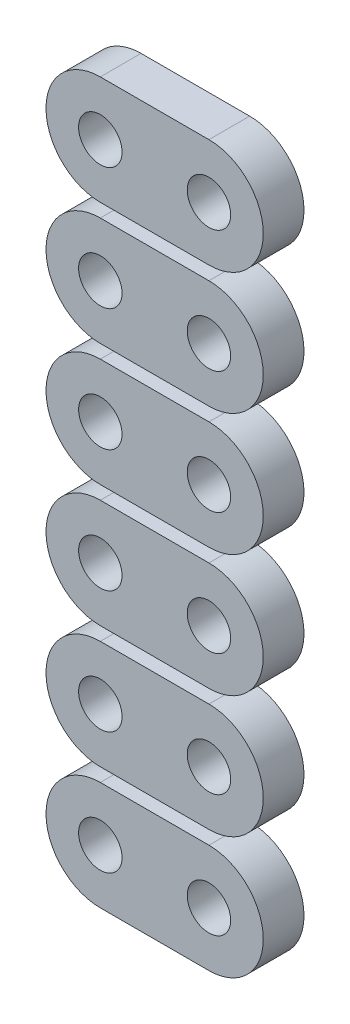
SolidWorks part; units mm, degrees
ref_plane "Front Plane" through (0, 0, 0) normal (0, 0, 1) x (1, 0, 0)
ref_plane "Top Plane" through (0, 0, 0) normal (0, 1, 0) x (1, 0, 0)
ref_plane "Right Plane" through (0, 0, 0) normal (1, 0, 0) x (0, 0, -1)
ref_axis "Axis2" through (-8.8, 0, 0) along (1, 0, 0)
ref_axis "Axis3" through (0, 4.4, 0) along (0, -1, 0)
sketch "Sketch1" plane through (0, 0, 0) normal (0, 0, 1) x (1, 0, 0)
  line L0 (-4, 0) -> (4, 0) construction
  line L1 (-4, 4) -> (4, 4)
  line L2 (-4, -4) -> (4, -4)
  arc A0 (-4, 4) -> (-4, -4) centre (-4, 0) ccw
  arc A1 (4, -4) -> (4, 4) centre (4, 0) ccw
  circle A2 centre (-4, 0) radius 1.6
  circle A3 centre (4, 0) radius 1.6
  point P2 (0, 0)
  dimension "D2" = 3.2
  dimension "D3" = 4
  dimension "D1" = 8
extrude "Main" add sketch "Sketch1" along normal blind 3
pattern_linear "LPattern4" count 6 spacing 9 along (0, -1, 0) of bodies 101
